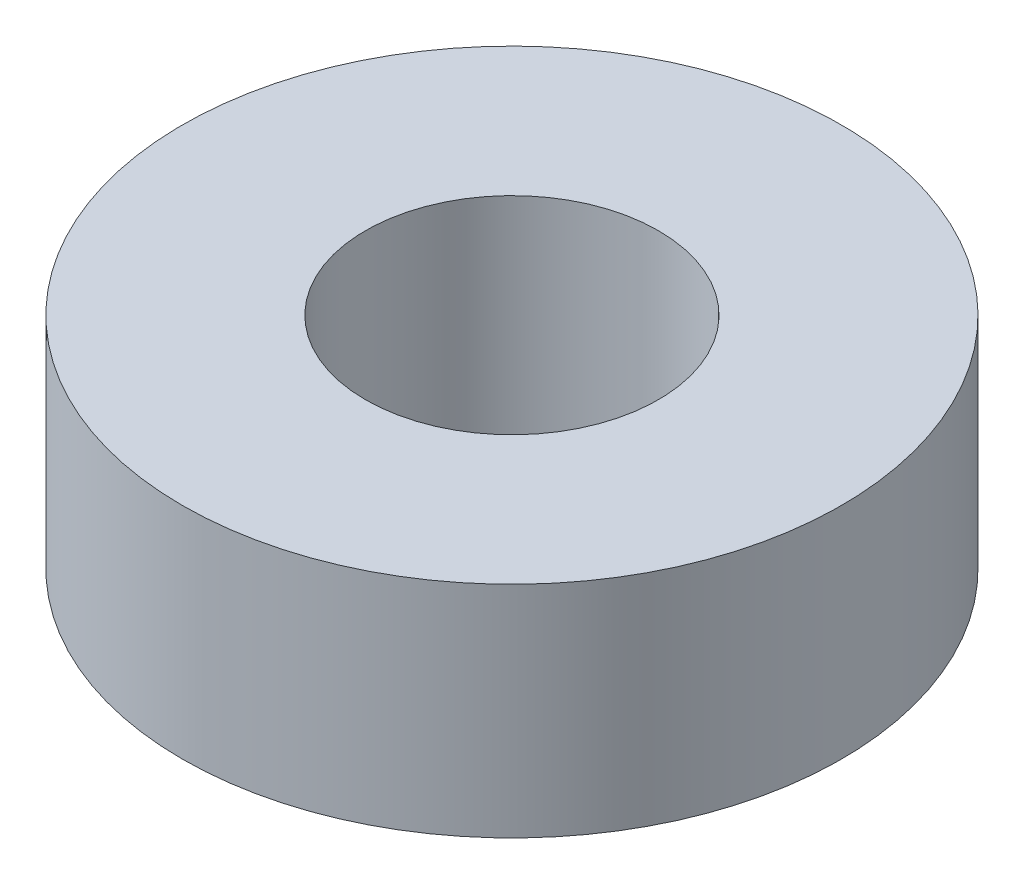
SolidWorks part; units mm, degrees
material "AISI 304"
ref_plane "Front Plane" through (0, 0, 0) normal (0, 0, 1) x (1, 0, 0)
ref_plane "Top Plane" through (0, 0, 0) normal (0, 1, 0) x (1, 0, 0)
ref_plane "Right Plane" through (0, 0, 0) normal (1, 0, 0) x (0, 0, -1)
sketch "Sketch1" plane through (0, 0, 0) normal (0, 1, 0) x (1, 0, 0)
  circle A0 centre (0, 0) radius 4.5
  dimension "D1" = 9
extrude "Boss-Extrude1" add sketch "Sketch1" along normal blind 3
hole_wizard "1/4 Clearance Hole1" positions "Sketch4" profile "Sketch3" hole size "1/4" standard "ANSI Inch" end condition through all
sketch "Sketch4" plane through (0, 3, 0) normal (0, 1, 0) x (1, 0, 0)
  point P0 (0, 0)
sketch "Sketch3" plane through (0, 3, 0) normal (1, 0, 0) x (0, 0, 1)
  line L0 (0, 0) -> (0, 3)
  line L1 (0, 3) -> (2, 3)
  line L2 (2, 3) -> (2, 0)
  line L5 (2, 0) -> (0, 0)
  line L11 (0, -6.35) -> (0, 107.95) construction
  dimension "Thru Hole Dia." = 4
  dimension "Thru Hole Depth" = 3
